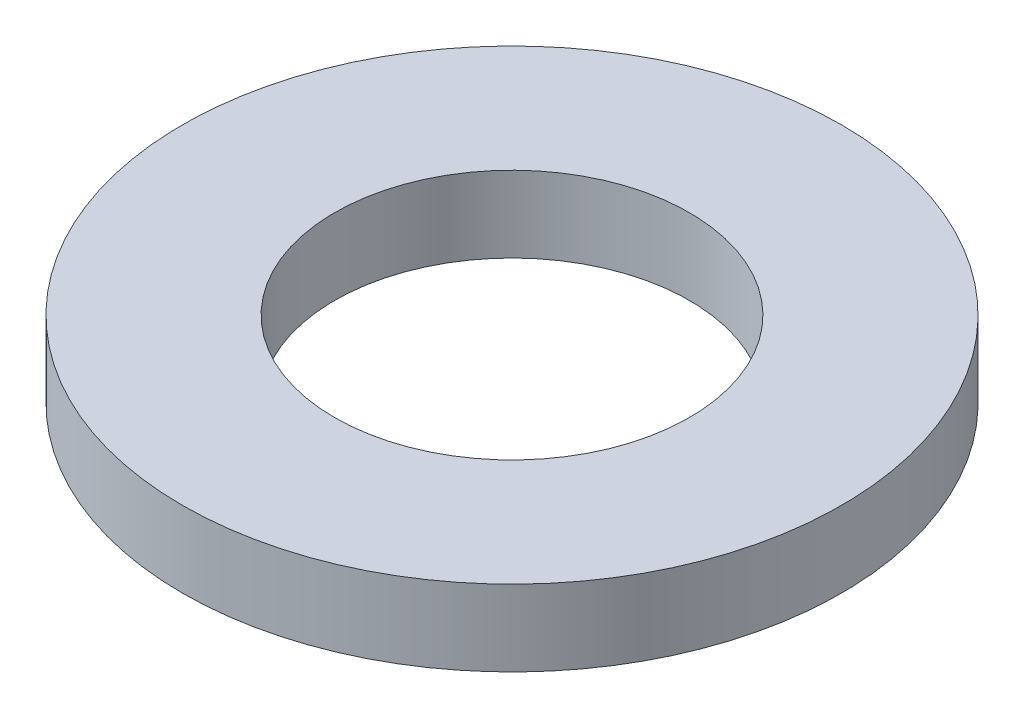
SolidWorks part; units mm, degrees
ref_plane "Front Plane" through (0, 0, 0) normal (0, 0, 1) x (1, 0, 0)
ref_plane "Top Plane" through (0, 0, 0) normal (0, 1, 0) x (1, 0, 0)
ref_plane "Right Plane" through (0, 0, 0) normal (1, 0, 0) x (0, 0, -1)
sketch "Sketch1" plane through (0, 0, 0) normal (0, 1, 0) x (1, 0, 0)
  circle A0 centre (0, 0) radius 65
  dimension "FLANGE_OD" = 130
extrude "Boss-Extrude1" add sketch "Sketch1" along normal blind 15
sketch "Sketch2" plane through (0, 0, 0) normal (0, 1, 0) x (1, 0, 0)
  circle A0 centre (0, 0) radius 35
  dimension "BORE_D" = 70
extrude "Cut-Extrude1" cut sketch "Sketch2" along normal through all
sketch "Sketch3" plane through (0, 15, 0) normal (0, 1, 0) x (1, 0, 0)
  circle A0 centre (0, 0) radius 29.6368 construction
  circle A1 centre (-29.6368, 0) radius 2.7164
  dimension "BOLT_D" = 5.4327
  dimension "BOLT_PCD" = 59.2736
extrude "Cut-Extrude2" cut sketch "Sketch3" against normal blind 10.2812 rebuild error yes
pattern_circular "CirPattern1" count 6 over 360 rebuild error yes
